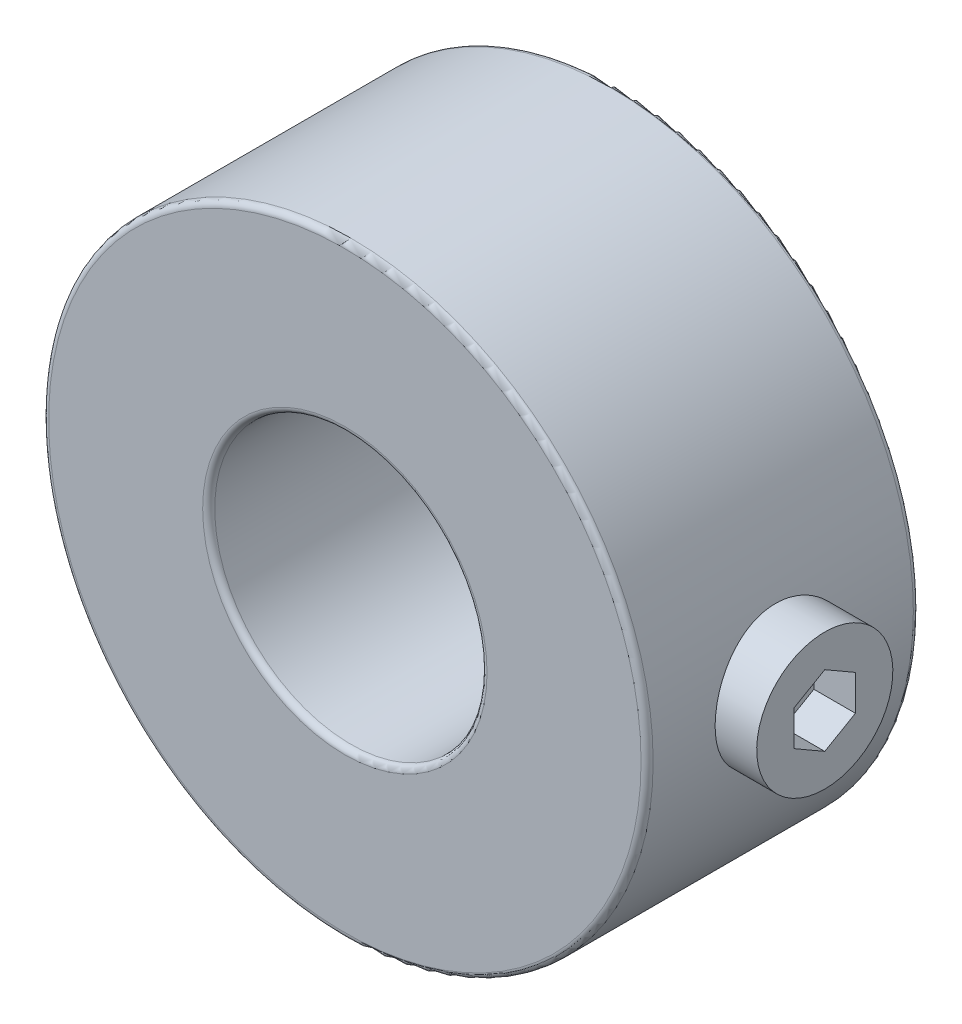
SolidWorks part; units mm, degrees
ref_plane "Front Plane" through (0, 0, 0) normal (0, 0, 1) x (1, 0, 0)
ref_plane "Top Plane" through (0, 0, 0) normal (0, 1, 0) x (1, 0, 0)
ref_plane "Right Plane" through (0, 0, 0) normal (1, 0, 0) x (0, 0, -1)
sketch "Sketch1" plane through (0, 0, 0) normal (0, 0, 1) x (1, 0, 0)
  circle A0 centre (0, 0) radius 11.1
  circle A1 centre (0, 0) radius 5
  point P4 (11.1, 0)
  dimension "Bore Dia" = 10
  dimension "OD" = 22.2
extrude "Extrude1" add sketch "Sketch1" along normal blind 10
ref_plane "Plane1" through (11.1, 0, 0) normal (1, 0, 0) x (0, 0, -1)
sketch "Sketch2" plane through (11.1, 0, 0) normal (1, 0, 0) x (0, 0, -1)
  line L0 (0, 0) -> (-10, 0) construction
  line L1 (-10, 11.1) -> (-10, -11.1) construction
  circle A0 centre (-5, 0) radius 2.5
  dimension "Set Screw Dia" = 5
extrude "Cut-Extrude1" cut sketch "Sketch2" against normal up to surface (11.1 mm away) up to plane "Right Plane"
ref_plane "Plane2" through (0, 0, 5) normal (0, 0, 1) x (1, 0, 0)
sketch "Sketch3" plane through (0, 0, 5) normal (0, 0, 1) x (1, 0, 0)
  line L1 (6.525, 0) -> (12.625, 0)
  line L2 (6.525, 0) -> (6.525, 2.5)
  line L3 (6.525, 2.5) -> (12.625, 2.5)
  line L4 (12.625, 0) -> (12.625, 2.5)
  line L5 (6.525, 0) -> (0, 0) construction
  dimension "D1" = 6.1
  dimension "D2" = 1.525
  dimension "D3" = 5
revolve "Revolve1" add sketch "Sketch3" angle 360 about L1
sketch "Sketch4" plane through (12.625, 0, 0) normal (1, 0, 0) x (0, 0, -1)
  line L1 (-5, 1.299) -> (-6.125, 0.6495)
  line L2 (-6.125, 0.6495) -> (-6.125, -0.6495)
  line L3 (-6.125, -0.6495) -> (-5, -1.299)
  line L4 (-5, -1.299) -> (-3.875, -0.6495)
  line L5 (-3.875, -0.6495) -> (-3.875, 0.6495)
  line L6 (-3.875, 0.6495) -> (-5, 1.299)
  circle A0 centre (-5, 0) radius 1.125 construction
  dimension "D1" = 2.25
extrude "Cut-Extrude2" cut sketch "Sketch4" against normal up to vertex (1.525 mm away) up to point (11.1, 0, 5)
fillet "Fillet1" radius 0.222 4 edges at (5, 0, 0) (5, 0, 10) (11.1, 0, 0) (11.1, 0, 10)
equation "\"D1@Sketch3\" = (\"OD@Sketch1\"-\"Bore Dia@Sketch1\")/2"
equation "\"D2@Sketch3\" = \"D1@Sketch3\"/4"
equation "\"D1@Sketch4\" = \"Set Screw Dia@Sketch2\"*.45"
equation "\"D3@Sketch3\" = \"Set Screw Dia@Sketch2\""
equation "\"D1@Fillet1\" = \"OD@Sketch1\"*.01"
